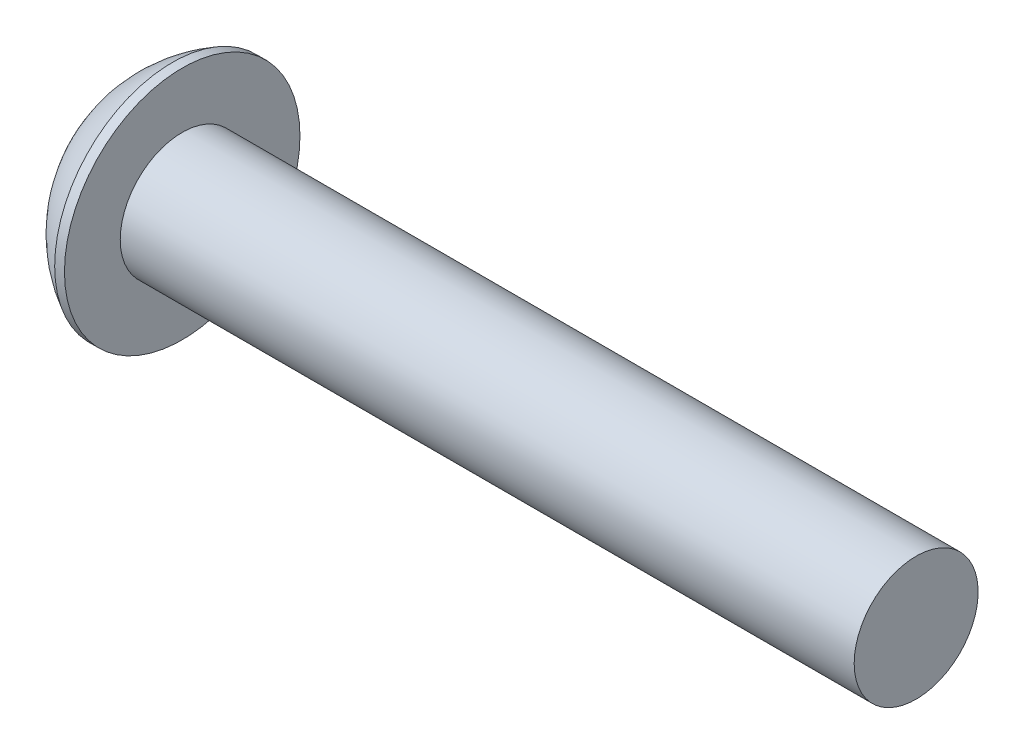
SolidWorks part; units mm, degrees
material "Alloy Steel"
ref_plane "Front" through (0, 0, 0) normal (0, 0, 1) x (1, 0, 0)
ref_plane "Top" through (0, 0, 0) normal (0, 1, 0) x (1, 0, 0)
ref_plane "Right" through (0, 0, 0) normal (1, 0, 0) x (0, 0, -1)
sketch "Sketch1" plane through (0, 0, 0) normal (0, 0, 1) x (1, 0, 0)
  line L0 (0, 0) -> (29.3116, 0)
  line L1 (29.3116, 0) -> (29.3116, 2.413)
  line L2 (29.3116, 2.413) -> (0.7366, 2.413)
  line L3 (0.7366, 2.413) -> (0.7366, 4.5847)
  line L4 (0.7366, 4.5847) -> (0.3556, 4.5847)
  line L5 (-1.8288, 2.413) -> (-1.8288, 1.8288)
  line L6 (0, 0) -> (4.2959, 0) construction
  line L7 (-1.8288, 1.8288) -> (0, 0)
  arc A0 (-1.8288, 2.413) -> (0.3556, 4.5847) centre (2.7515, -0.0097) cw
  dimension "Head Radius" = 5.1816
  dimension "Edge Flat" = 0.381
  dimension "Thread Length" = 28.575
  dimension "Head Diameter" = 9.1694
  dimension "Thread Diameter" = 4.826
  dimension "D6" = 45
  dimension "Head Height" = 2.5654
  dimension "Hex Chamfer Radius" = 1.8288
revolve "Revolve1" add sketch "Sketch1" angle 360 about L6
sketch "Sketch2" plane through (-1.8288, 0, 0) normal (-1, 0, 0) x (0, 0, 1)
  line L1 (1.8331, 0) -> (0.9165, 1.5875)
  line L2 (0.9165, 1.5875) -> (-0.9165, 1.5875)
  line L3 (-0.9165, 1.5875) -> (-1.8331, 0)
  line L4 (-1.8331, 0) -> (-0.9165, -1.5875)
  line L5 (-0.9165, -1.5875) -> (0.9165, -1.5875)
  line L6 (0.9165, -1.5875) -> (1.8331, 0)
  circle A0 centre (0, 0) radius 1.5875 construction
  dimension "Hex Width" = 3.175
extrude "Cut-Extrude1" cut sketch "Sketch2" against normal up to vertex (1.8288 mm away) up to point (0, 0, 0)
other "Freeze***"
